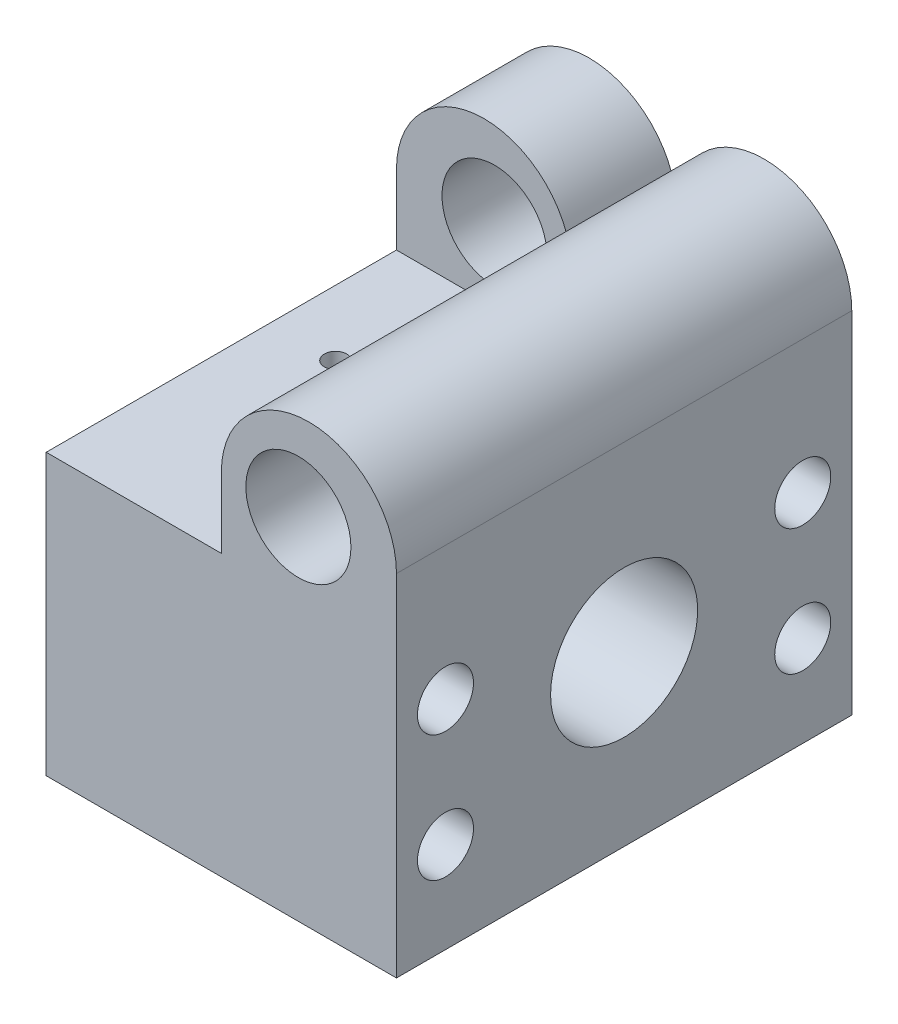
SolidWorks part; units mm, degrees
material "ABS"
ref_plane "Front Plane" through (0, 0, 0) normal (0, 0, 1) x (1, 0, 0)
ref_plane "Top Plane" through (0, 0, 0) normal (0, 1, 0) x (1, 0, 0)
ref_plane "Right Plane" through (0, 0, 0) normal (1, 0, 0) x (0, 0, -1)
sketch "Sketch1" plane through (0, 0, 0) normal (0, 0, 1) x (1, 0, 0)
  line L0 (0, 0) -> (50, 0)
  line L1 (50, 0) -> (50, 50)
  line L2 (0, 50) -> (0, 0)
  arc A0 (50, 50) -> (25, 58.6603) centre (36, 50) ccw
  arc A1 (25, 58.6603) -> (0, 50) centre (14, 50) ccw
  circle A2 centre (36, 50) radius 7.5
  circle A3 centre (14, 50) radius 7.5
  dimension "D2" = 22
  dimension "D5" = 15
  dimension "D1" = 50
  dimension "D4" = 50
extrude "Boss-Extrude1" add sketch "Sketch1" along normal blind 15
sketch "Sketch2" plane through (0, 0, 15) normal (0, 0, 1) x (1, 0, 0)
  line L0 (0, 0) -> (0, 50)
  line L4 (25, 50) -> (25, 0)
  line L5 (25, 0) -> (0, 0)
  line L6 (25, 0) -> (50, 0)
  line L7 (50, 0) -> (50, 50)
  line L8 (0, 0) -> (25, 0)
  circle A1 centre (14, 50) radius 7.5
  circle A2 centre (36, 50) radius 7.5 construction
  circle A3 centre (14, 50) radius 7.5 construction
  arc A4 (0, 50) -> (25, 50) centre (12.5, 50) cw
  arc A5 (50, 50) -> (25, 50) centre (37.5, 50) ccw
  line M7 (0, 0) -> (50, 0)
  line M8 (50, 0) -> (50, 50)
  arc M9 (50, 50) -> (25, 58.6603) centre (36, 50) ccw
  arc M10 (25, 58.6603) -> (0, 50) centre (14, 50) ccw
  circle M11 centre (36, 50) radius 7.5
extrude "Boss-Extrude2" add sketch "Sketch2" along normal blind 50 contours A5 L4 M8 M7 M11 region at (37.701, 27.2902, 15)
sketch "Sketch3" plane through (0, 0, 0) normal (0, 0, -1) x (-1, 0, 0)
  line L0 (0, 50) -> (0, 0) construction
  line L1 (-50, 0) -> (0, 0)
  line L2 (-50, 0) -> (-50, 40)
  line L3 (-50, 40) -> (0, 40)
  line L4 (0, 0) -> (0, 40)
  dimension "D1" = 40
extrude "Boss-Extrude3" add sketch "Sketch3" against normal blind 65
extrude "Cut-Extrude2" cut sketch "Sketch2<3>" against normal through all contours A5 A4 M9 M10 region at (9.5874, 62.7381, 15)
sketch "Sketch2<3>" plane through (0, 0, 15) normal (0, 0, 1) x (1, 0, 0) same geometry as "Sketch2"
sketch "Sketch9" plane through (0, 0, 0) normal (-1, 0, 0) x (0, 0, 1)
  line L0 (0, 50) -> (0, 0) construction
  line L1 (65, 0) -> (0, 0) construction
  line L2 (65, 0) -> (65, 40) construction
  circle A1 centre (7, 13) radius 4
  circle A3 centre (58, 13) radius 4
  circle A4 centre (58, 31) radius 4
  circle A5 centre (7, 31) radius 4
  circle A6 centre (32.5, 24) radius 10.5
  dimension "D1" = 8
  dimension "D2" = 13
  dimension "D3" = 7
  dimension "D4" = 7
  dimension "D5" = 18
  dimension "D6" = 21
  dimension "D7" = 24
  dimension "D8" = 32.5
extrude "Cut-Extrude3" cut sketch "Sketch9" against normal through all
sketch "Sketch10" plane through (0, 40, 0) normal (0, 1, 0) x (1, 0, 0)
  line L1 (25, 0) -> (0, 0) construction
  circle A0 centre (9.3061, -33) radius 1.6
  dimension "D1" = 3.2
  dimension "D2" = 33
extrude "Cut-Extrude4" cut sketch "Sketch10" along normal through all and the other way through all
